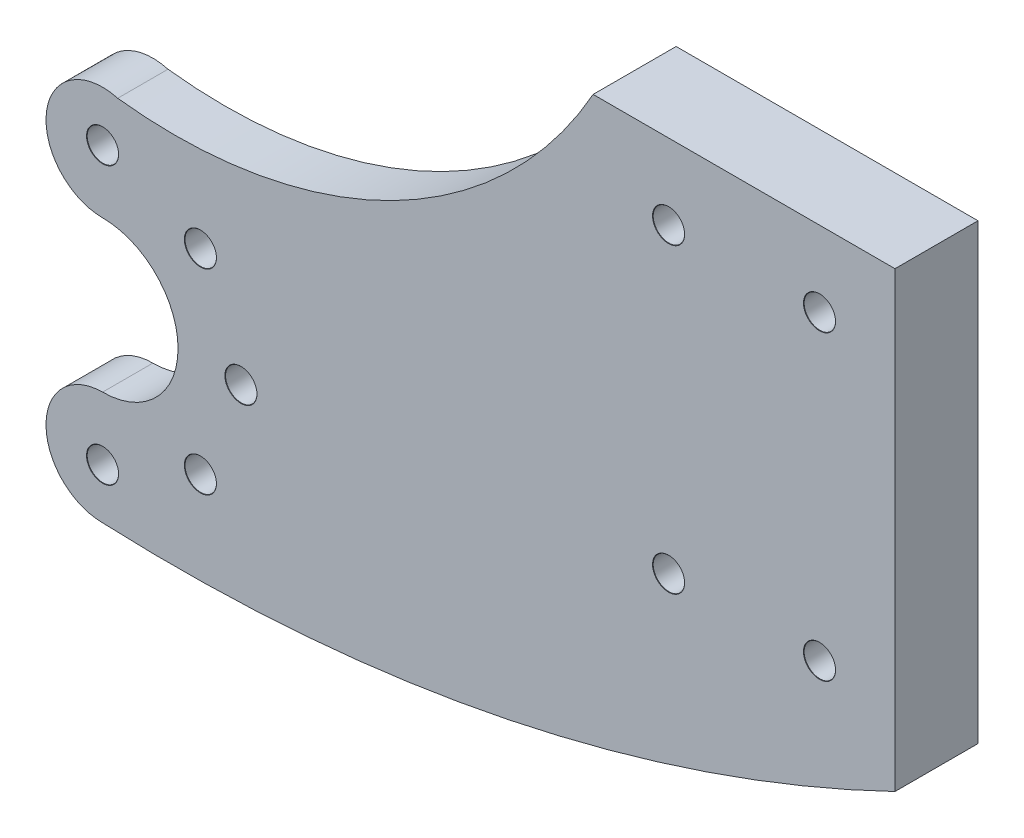
SolidWorks part; units mm, degrees
ref_plane "前视基准面" through (0, 0, 0) normal (0, 0, 1) x (1, 0, 0)
ref_plane "上视基准面" through (0, 0, 0) normal (0, 1, 0) x (1, 0, 0)
ref_plane "右视基准面" through (0, 0, 0) normal (1, 0, 0) x (0, 0, -1)
sketch "草图1" plane through (0, 0, 0) normal (0, 0, 1) x (1, 0, 0)
  line L1 (0, 0) -> (-24, 0)
  line L2 (0, 0) -> (0, 36)
  line L3 (0, 36) -> (-24, 36)
  line L4 (-24, 0) -> (-24, 36)
  dimension "D1" = 36
  dimension "D2" = 24
extrude "凸台-拉伸1" add sketch "草图1" along normal blind 2.6
sketch "草图4" plane through (0, 0, 2.6) normal (0, 0, 1) x (1, 0, 0)
  line L0 (-63, 16.999) -> (-63, -12.999)
  line L1 (-12, 36) -> (-12, 0) construction
  line L2 (-24, 36) -> (0, 36)
  line L3 (0, 36) -> (0, 0)
  line L4 (-63, 2) -> (-77.0817, 2) construction
  line L5 (-24, 18) -> (0, 18) construction
  line L6 (-24, 36) -> (-24, 0) construction
  line L7 (-63, 16.999) -> (-63, 8)
  line L8 (-63, -12.999) -> (-63, -4)
  arc A3 (-63, -12.999) -> (0, 0) centre (-57.2579, 118.3371) ccw
  arc A4 (-63, 16.999) -> (-24, 36) centre (-57.2497, 54.7211) ccw
  circle A5 centre (-63, 2) radius 6
  circle A6 centre (-63, 12.5) radius 4.499
  circle A7 centre (-63, -8.5) radius 4.499
  point P18 (-57, 7.8093)
  point P27 (-63, 16.999)
  line M7 (0, 0) -> (0, 36)
  line M8 (0, 36) -> (-24, 36)
  line M9 (-24, 36) -> (-24, 0)
  line M10 (-24, 0) -> (0, 0)
  dimension "D4" = 16
  dimension "D6" = 12
  dimension "D3" = 51
extrude "凸台-拉伸2" add sketch "草图4" along normal blind 4 contours A5 L0 A3 A4 M10 M9 | M10 M7 M8 M9 | A6 | A7 region at (-38.1122, 4.6974, 2.6) region at (-12, 18, 2.6)
hole_wizard "Ø2.5mm 暗销孔1" positions "草图5" profile "草图6" hole size "Ø2.5" standard "ISO" end condition through all
sketch "草图5" plane through (0, 0, 6.6) normal (0, 0, 1) x (1, 0, 0)
  line L0 (-63, 2) -> (-63, 12.3527) construction
  circle A1 centre (-63, 2) radius 1.4731 construction
  point P14 (-63, 13)
  point P21 (-55.2218, 9.7782)
  point P22 (-52, 2)
  point P23 (-55.2218, -5.7782)
  point P24 (-63, -9)
  dimension "D1" = 11
  dimension "D2" = 5
sketch "草图6" plane through (-63, -9, 6.6) normal (1, 0, 0) x (0, -1, 0)
  line L0 (0, 0) -> (0, 6.6)
  line L1 (0, 6.6) -> (1.25, 6.6)
  line L2 (1.25, 6.6) -> (1.25, 0.025)
  line L3 (1.25, 0.025) -> (1.275, 0)
  line L5 (1.275, 0) -> (0, 0)
  line L6 (-1.25, 0.025) -> (-1.275, 0) construction
  line L11 (0, -6.35) -> (0, 107.95) construction
  dimension "通孔孔直径" = 2.5
  dimension "通孔孔深度" = 6.6
  dimension "近端锥形沉头孔直径" = 2.55
  dimension "近端锥形沉头孔角度" = 90
hole_wizard "Ø2.5mm 暗销孔2" positions "草图7" profile "草图8" hole size "Ø2.5" standard "ISO" end condition through all
sketch "草图7" plane through (0, 0, 6.6) normal (0, 0, 1) x (1, 0, 0)
  line L0 (-12, 36) -> (-12, -8.6488) construction
  line L3 (0, 18) -> (-41.4541, 18) construction
  point P17 (-18, 30)
  point P19 (-18, 6)
  point P21 (-6, 6)
  point P22 (-6, 30)
  dimension "D1" = 24
  dimension "D2" = 12
  dimension "D3" = 6
  dimension "D4" = 6
sketch "草图8" plane through (-6, 30, 6.6) normal (1, 0, 0) x (0, -1, 0)
  line L0 (0, 0) -> (0, 6.6)
  line L1 (0, 6.6) -> (1.25, 6.6)
  line L2 (1.25, 6.6) -> (1.25, 0.025)
  line L3 (1.25, 0.025) -> (1.275, 0)
  line L5 (1.275, 0) -> (0, 0)
  line L6 (-1.25, 0.025) -> (-1.275, 0) construction
  line L11 (0, -6.35) -> (0, 107.95) construction
  dimension "通孔孔直径" = 2.5
  dimension "通孔孔深度" = 6.6
  dimension "近端锥形沉头孔直径" = 2.55
  dimension "近端锥形沉头孔角度" = 90
